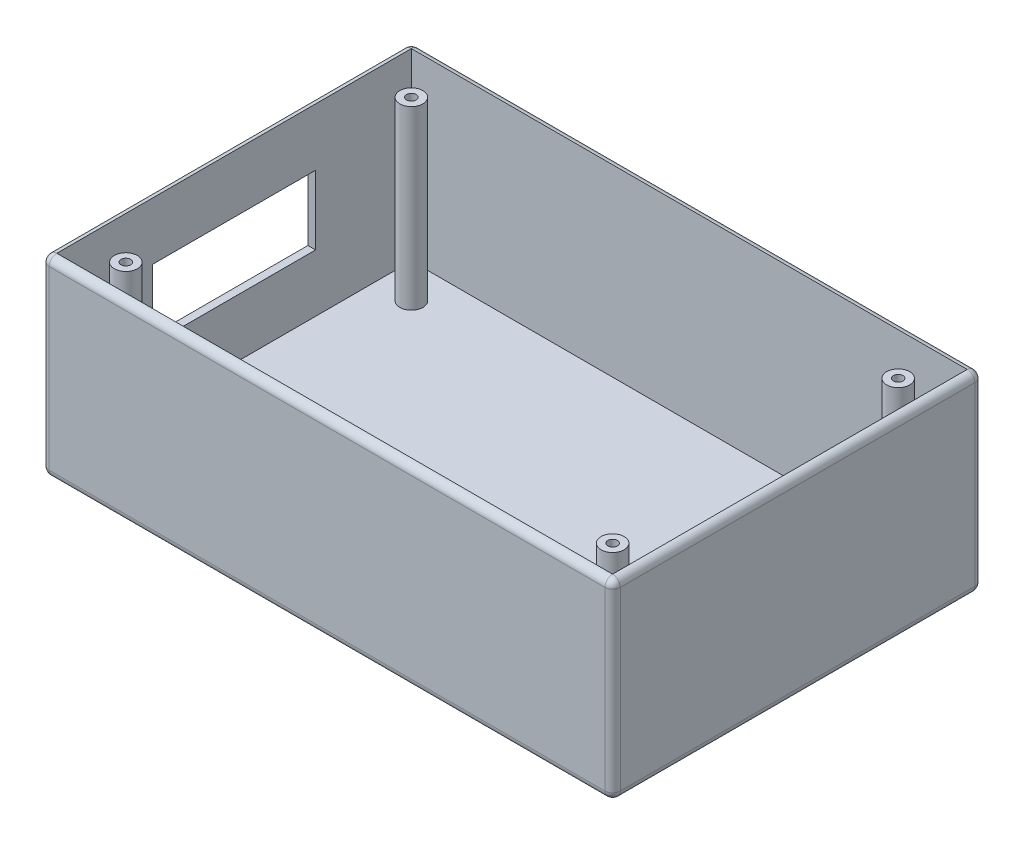
SolidWorks part; units mm, degrees
ref_plane "Front Plane" through (0, 0, 0) normal (0, 0, 1) x (1, 0, 0)
ref_plane "Top Plane" through (0, 0, 0) normal (0, 1, 0) x (1, 0, 0)
ref_plane "Right Plane" through (0, 0, 0) normal (1, 0, 0) x (0, 0, -1)
sketch "Sketch1" plane through (0, 0, 0) normal (0, 1, 0) x (1, 0, 0)
  line L1 (-74.5, 48.25) -> (74.5, 48.25)
  line L2 (-74.5, 48.25) -> (-74.5, -48.25)
  line L3 (-74.5, -48.25) -> (74.5, -48.25)
  line L4 (74.5, 48.25) -> (74.5, -48.25)
  line L5 (-74.5, 48.25) -> (74.5, -48.25) construction
  line L6 (-74.5, -48.25) -> (74.5, 48.25) construction
  point P0 (0, 0)
  dimension "D1" = 96.5
  dimension "D2" = 149
extrude "Boss-Extrude1" add sketch "Sketch1" along normal blind 50
shell "Shell2" thickness 2 removed face at (0, 50, 0)
sketch "Sketch2" plane through (0, 2, 0) normal (0, 1, 0) x (1, 0, 0)
  line L0 (74.5, 48.25) -> (-74.5, 48.25) construction
  line L1 (-74.5, 48.25) -> (-74.5, -48.25) construction
  line L2 (0, 21.258) -> (0, -8.3513)
  line L3 (0, 6.4534) -> (16.8826, 6.4534)
  line L4 (63.5, 0) -> (30.7989, 0)
  circle A0 centre (-63.5, 37.25) radius 3
  circle A1 centre (63.5, 37.25) radius 3
  circle A2 centre (-63.5, -37.25) radius 3
  circle A3 centre (63.5, -37.25) radius 3
  dimension "D1" = 6
  dimension "D2" = 11
  dimension "D3" = 11
extrude "Boss-Extrude2" add sketch "Sketch2" along normal blind 46 contours A0 | A1 | A3 | A2 region at (-63.5, 2, -37.25) region at (63.5, 2, -37.25) region at (-63.5, 2, 37.25) region at (63.5, 2, 37.25)
sketch "Sketch3" plane through (-72.5, 0, 0) normal (1, 0, 0) x (0, 0, -1)
  line L0 (46.25, 50) -> (-46.25, 50) construction
  line L1 (-21.25, 35) -> (21.25, 35)
  line L2 (-21.25, 35) -> (-21.25, 17)
  line L3 (-21.25, 17) -> (21.25, 17)
  line L4 (21.25, 35) -> (21.25, 17)
  line L5 (46.25, 2) -> (-46.25, 2) construction
  line L6 (46.25, 50) -> (46.25, 2) construction
  line L7 (-46.25, 50) -> (-46.25, 2) construction
  dimension "D1" = 15
  dimension "D2" = 15
  dimension "D3" = 25
  dimension "D4" = 25
extrude "Cut-Extrude1" cut sketch "Sketch3" against normal blind 46
sketch "Sketch4" plane through (0, 48, 0) normal (0, 1, 0) x (1, 0, 0)
  line L0 (0, 5.5333) -> (0, -14.899)
  line L1 (12.0808, 0) -> (-17.2907, 0)
  circle A0 centre (-63.5, 37.25) radius 1.25
  circle A1 centre (63.5, 37.25) radius 1.25
  circle A2 centre (63.5, -37.25) radius 1.25
  circle A3 centre (-63.5, -37.25) radius 1.25
  dimension "D1" = 2.5
extrude "Cut-Extrude2" cut sketch "Sketch4" against normal up to surface (46 mm away) contours A2 | A0 | A3 | A1 region at (63.5, 48, 37.25) up to face at (-63.5, 2, 40.25)
fillet "Fillet1" radius 2 12 edges at (74.5, 50, 0) (74.5, 25, -48.25) (74.5, 0, 0) (-74.5, 25, 48.25) (0, 50, 48.25) (74.5, 25, 48.25) (0, 0, 48.25) (-74.5, 50, 0) (0, 0, -48.25) (0, 50, -48.25) (-74.5, 0, 0) (-74.5, 25, -48.25)
